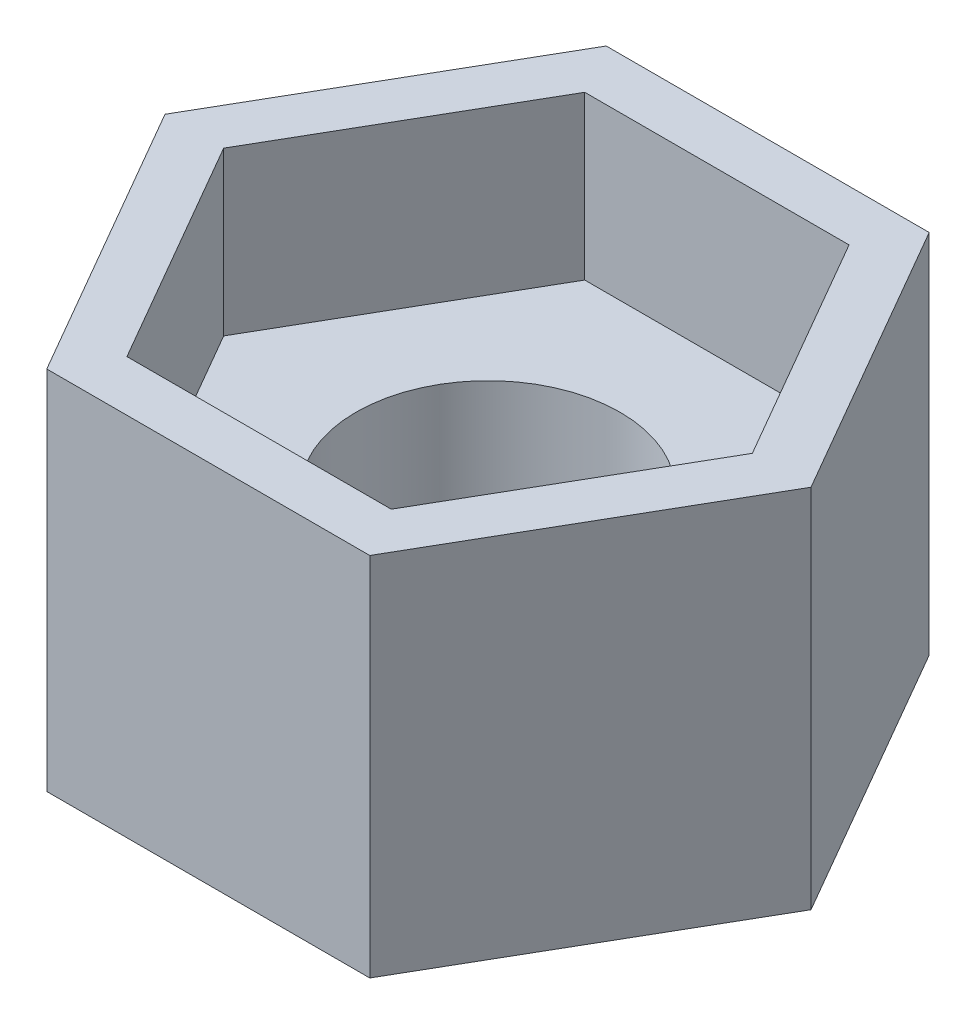
SolidWorks part; units mm, degrees
ref_plane "Front" through (0, 0, 0) normal (0, 0, 1) x (1, 0, 0)
ref_plane "Top" through (0, 0, 0) normal (0, 1, 0) x (1, 0, 0)
ref_plane "Right" through (0, 0, 0) normal (1, 0, 0) x (0, 0, -1)
sketch "Sketch1" plane through (0, 0, 0) normal (0, 1, 0) x (1, 0, 0)
  line L1 (1, -1.7321) -> (2, 0)
  line L2 (2, 0) -> (1, 1.7321)
  line L3 (1, 1.7321) -> (-1, 1.7321)
  line L4 (-1, 1.7321) -> (-2, 0)
  line L5 (-2, 0) -> (-1, -1.7321)
  line L6 (-1, -1.7321) -> (1, -1.7321)
  line L7 (1.3002, -2.2521) -> (2.6004, 0)
  line L8 (2.6004, 0) -> (1.3002, 2.2521)
  line L9 (1.3002, 2.2521) -> (-1.3002, 2.2521)
  line L10 (-1.3002, 2.2521) -> (-2.6004, 0)
  line L11 (-2.6004, 0) -> (-1.3002, -2.2521)
  line L12 (-1.3002, -2.2521) -> (1.3002, -2.2521)
  line L13 (3.1778, 0) -> (1.5889, 2.7521)
  line L14 (1.5889, 2.7521) -> (-1.5889, 2.7521)
  line L15 (-1.5889, 2.7521) -> (-3.1778, 0)
  line L16 (-3.1778, 0) -> (-1.5889, -2.7521)
  line L17 (-1.5889, -2.7521) -> (1.5889, -2.7521)
  line L18 (1.5889, -2.7521) -> (3.1778, 0)
  circle A0 centre (0, 0) radius 1.7321 construction
  circle A1 centre (0, 0) radius 2.2521 construction
  circle A2 centre (0, 0) radius 2.7521 construction
  dimension "D1" = 2
  dimension "D2" = 0.52
  dimension "D3" = 0.5
extrude "Boss-Extrude1" add sketch "Sketch1" against normal blind 1 contours L5 L6 L1 L2 L3 L4 | L11 L12 L7 L8 L9 L10 L6 L5 L4 L3 L2 L1 | L17 L18 L13 L14 L15 L16 L12 L11 L10 L9 L8 L7 region at (0, 0, 0) region at (0, 0, 2.1832) region at (2.3105, 0, 1.334)
extrude "Boss-Extrude2" add sketch "Sketch1<3>" along normal blind 1.6 contours L17 L18 L13 L14 L15 L16 L12 L11 L10 L9 L8 L7 region at (2.3105, 0, 1.334)
sketch "Sketch1<3>" plane through (0, 0, 0) normal (0, 1, 0) x (1, 0, 0) same geometry as "Sketch1"
sketch "Sketch2" plane through (0, -1, 0) normal (0, -1, 0) x (1, 0, 0)
  circle A0 centre (0, 0) radius 1.3
  dimension "D1" = 2.6
extrude "Cut-Extrude1" cut sketch "Sketch2" against normal blind 2.6
sketch "Sketch3" plane through (0, -1, 0) normal (0, -1, 0) x (1, 0, 0)
  line L1 (-1.5889, -2.7521) -> (1.5889, -2.7521)
  line L2 (1.5889, -2.7521) -> (3.1778, 0)
  line L3 (3.1778, 0) -> (1.5889, 2.7521)
  line L4 (1.5889, 2.7521) -> (-1.5889, 2.7521)
  line L5 (-1.5889, 2.7521) -> (-3.1778, 0)
  line L6 (-3.1778, 0) -> (-1.5889, -2.7521)
  circle A0 centre (0, 0) radius 2.7521 construction
  circle A1 centre (0, 0) radius 1.3
extrude "Boss-Extrude3" add sketch "Sketch3" along normal blind 1
